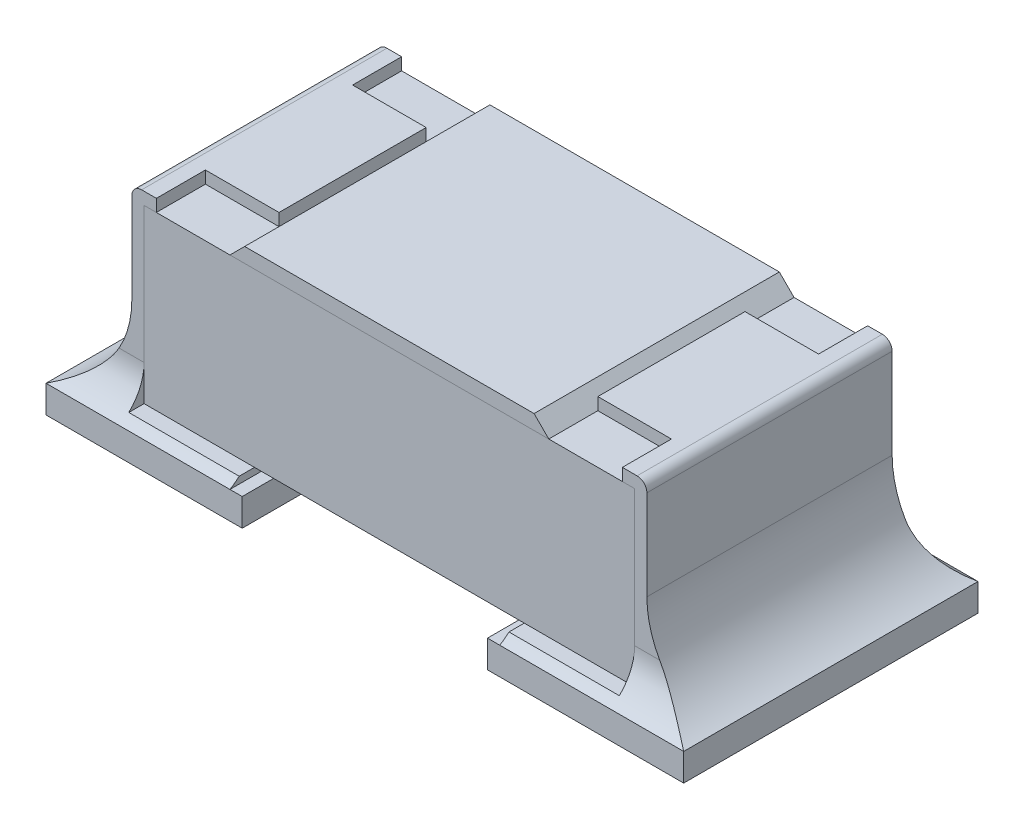
SolidWorks part; units mm, degrees
material "Ceramic Porcelain"
ref_plane "Front Plane" through (0, 0, 0) normal (0, 0, 1) x (1, 0, 0)
ref_plane "Top Plane" through (0, 0, 0) normal (0, 1, 0) x (1, 0, 0)
ref_plane "Right Plane" through (0, 0, 0) normal (1, 0, 0) x (0, 0, -1)
sketch "Sketch1" plane through (0, 0, 0) normal (1, 0, 0) x (0, 0, -1)
  line L0 (0, 55) -> (0, -55) construction
  line L1 (-0.25, 0.42) -> (0.25, 0.42)
  line L2 (-0.25, 0.42) -> (-0.25, 0.07)
  line L3 (-0.25, 0.07) -> (0.25, 0.07)
  line L4 (0.25, 0.42) -> (0.25, 0.07)
  line L5 (55, 0) -> (-55, 0) construction
  dimension "D1" = 0.5
  dimension "D2" = 0.25
  dimension "D3" = 0.35
  dimension "D4" = 0.07
extrude "Boss-Extrude1" add sketch "Sketch1" along normal mid plane 1
sketch "Sketch2" plane through (0, 0, 0) normal (0, 0, 1) x (1, 0, 0)
  line L0 (-0.325, 0.445) -> (-0.505, 0.445)
  line L1 (-0.525, 0.425) -> (-0.525, 0.045)
  line L2 (-0.525, 0.045) -> (-0.275, 0.045)
  line L3 (-0.275, 0.045) -> (-0.275, 0.07)
  line L4 (0.5, 0.07) -> (-0.5, 0.07) construction
  line L5 (-0.275, 0.07) -> (-0.5, 0.07)
  line L6 (-0.5, 0.07) -> (-0.5, 0.42)
  line L7 (-0.5, 0.42) -> (-0.325, 0.42)
  line L8 (0.5, 0.42) -> (-0.5, 0.42) construction
  line L9 (-0.325, 0.42) -> (-0.325, 0.445)
  line L11 (0.325, 0.42) -> (0.325, 0.445)
  line L12 (0.325, 0.445) -> (0.505, 0.445)
  line L13 (0.525, 0.425) -> (0.525, 0.045)
  line L14 (0.525, 0.045) -> (0.275, 0.045)
  line L15 (0.275, 0.045) -> (0.275, 0.07)
  line L16 (0.275, 0.07) -> (0.5, 0.07)
  line L17 (0.5, 0.07) -> (0.5, 0.42)
  line L18 (0.5, 0.42) -> (0.325, 0.42)
  arc A0 (0.505, 0.445) -> (0.525, 0.425) centre (0.505, 0.425) cw
  arc A1 (-0.505, 0.445) -> (-0.525, 0.425) centre (-0.505, 0.425) ccw
  point P28 (-0.525, 0.445)
  dimension "D6" = 0.02
  dimension "D1" = 0.025
  dimension "D2" = 0.025
  dimension "D3" = 0.025
  dimension "D4" = 0.2
  dimension "D5" = 0.25
extrude "Boss-Extrude2" add sketch "Sketch2" along normal mid plane 0.5 separate body
sketch "Sketch3" plane through (0, 0.445, 0) normal (0, 1, 0) x (1, 0, 0)
  line L0 (0.325, -0.25) -> (0.325, 0.25) construction
  line L1 (-0.325, 0.25) -> (-0.475, 0.25)
  line L2 (-0.325, 0.25) -> (-0.325, 0.15)
  line L3 (-0.325, 0.15) -> (-0.475, 0.15)
  line L4 (-0.475, 0.25) -> (-0.475, 0.15)
  line L5 (-0.325, -0.25) -> (-0.475, -0.25)
  line L6 (-0.325, -0.25) -> (-0.325, -0.15)
  line L7 (-0.325, -0.15) -> (-0.475, -0.15)
  line L8 (-0.475, -0.25) -> (-0.475, -0.15)
  line L9 (0.325, -0.25) -> (0.475, -0.25)
  line L10 (0.325, -0.25) -> (0.325, -0.15)
  line L11 (0.325, -0.15) -> (0.475, -0.15)
  line L12 (0.475, -0.25) -> (0.475, -0.15)
  line L13 (0.5, -0.25) -> (-0.5, -0.25) construction
  line L15 (0.325, 0.25) -> (0.475, 0.25)
  line L16 (0.325, 0.25) -> (0.325, 0.15)
  line L17 (0.325, 0.15) -> (0.475, 0.15)
  line L18 (0.475, 0.25) -> (0.475, 0.15)
  dimension "D1" = 0.15
  dimension "D2" = 0.1
extrude "Cut-Extrude1" cut sketch "Sketch3" against normal blind 0.025
sketch "Sketch4" plane through (0, 0, 0) normal (0, 0, 1) x (1, 0, 0)
  line L0 (-0.325, 0.42) -> (0.325, 0.42)
  line L1 (0.325, 0.42) -> (0.295, 0.45)
  line L2 (0.295, 0.45) -> (-0.295, 0.45)
  line L3 (-0.295, 0.45) -> (-0.325, 0.42)
  dimension "D1" = 45
  dimension "D2" = 45
  dimension "D3" = 0.03
extrude "Boss-Extrude3" add sketch "Sketch4" along normal mid plane 0.5 separate body
sketch "Sketch7" plane through (0, 0, 0) normal (0, 1, 0) x (1, 0, 0)
  line L0 (0, -0.2228) -> (0, 0.2228) construction
  line L1 (-0.25, -0.3) -> (-0.65, -0.3)
  line L2 (-0.25, -0.3) -> (-0.25, 0.3)
  line L3 (-0.25, 0.3) -> (-0.65, 0.3)
  line L4 (-0.65, -0.3) -> (-0.65, 0.3)
  line L5 (0.25, -0.3) -> (0.65, -0.3)
  line L6 (0.25, -0.3) -> (0.25, 0.3)
  line L7 (0.25, 0.3) -> (0.65, 0.3)
  line L8 (0.65, -0.3) -> (0.65, 0.3)
  line L9 (-0.2228, 0) -> (0.2228, 0) construction
  dimension "D1" = 0.4
  dimension "D2" = 0.25
  dimension "D3" = 0.25
  dimension "D4" = 0.6
  dimension "D5" = 0.3
extrude "Boss-Extrude5" add sketch "Sketch7" along normal blind 0.056
fillet "Fillet3" radius 0.2 1 edges at (-0.525, 0.056, 0)
fillet "Fillet4" radius 0.2 1 edges at (0.525, 0.056, 0)
fillet "Fillet5" radius 0.1 2 edges at (0.4625, 0.056, -0.25) (0.4625, 0.056, 0.25)
fillet "Fillet6" radius 0.1 2 edges at (-0.4625, 0.056, 0.25) (-0.4625, 0.056, -0.25)
ref_axis "Axis1" through (0, 0.4725, 0) along (0, -1, 0)
